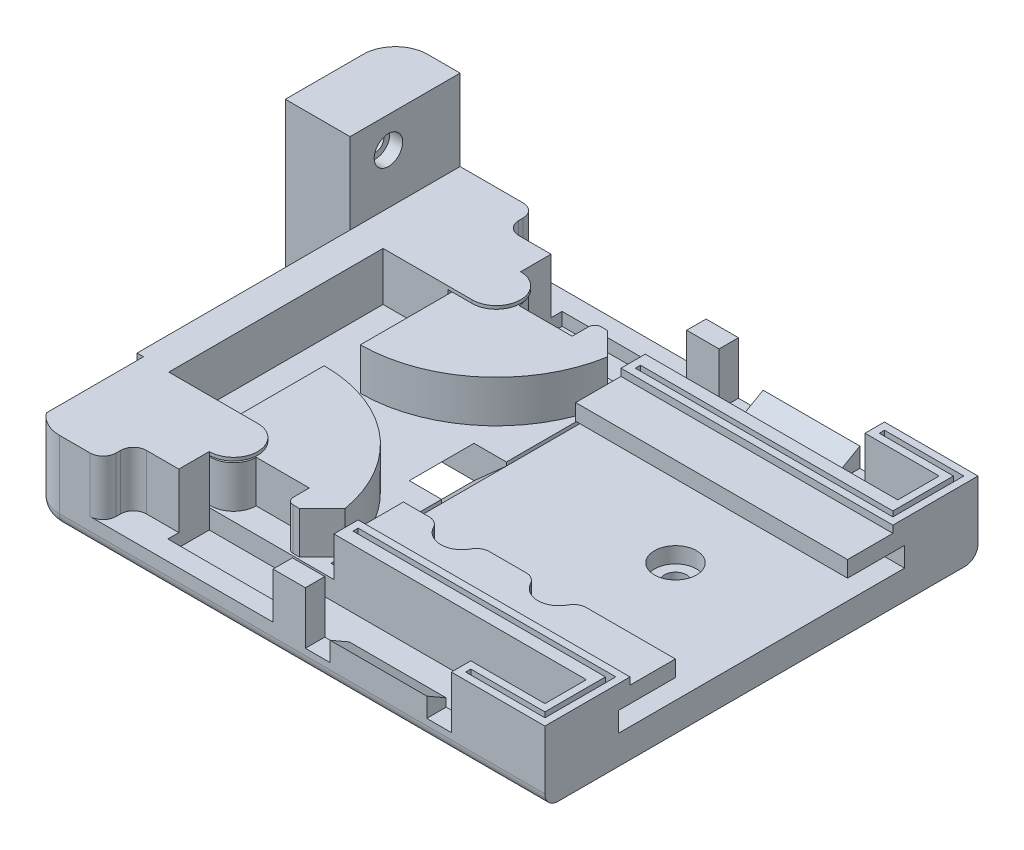
SolidWorks part; units mm, degrees
ref_plane "Front Plane" through (0, 0, 0) normal (0, 0, 1) x (1, 0, 0)
ref_plane "Top Plane" through (0, 0, 0) normal (0, 1, 0) x (1, 0, 0)
ref_plane "Right Plane" through (0, 0, 0) normal (1, 0, 0) x (0, 0, -1)
sketch "Sketch1" plane through (0, 0, 0) normal (0, 1, 0) x (1, 0, 0)
  line L0 (5, 33.45) -> (5, 16.9)
  line L1 (0, 0) -> (80, 0)
  line L2 (0, 0) -> (0, 33.45)
  line L3 (0, 33.45) -> (80, 33.45)
  line L4 (80, 0) -> (80, 33.45)
  line L5 (5, 16.9) -> (15, 16.9)
  line L6 (15, 16.9) -> (15, 13.15)
  line L7 (18.75, 9.4) -> (18.75, 3)
  line L8 (18.75, 3) -> (77, 3)
  line L10 (18.75, 9.4) -> (77, 9.4)
  line L11 (77, 3) -> (77, 9.4)
  line L12 (38, 9.4) -> (80, 9.4)
  line L13 (38, 9.4) -> (38, 13.15)
  line L14 (38, 13.15) -> (80, 13.15)
  line L15 (80, 9.4) -> (80, 13.15)
  circle A0 centre (18.75, 13.15) radius 2.25
  arc A1 (15, 13.15) -> (18.75, 9.4) centre (18.75, 13.15) ccw
  circle A2 centre (18.75, 13.15) radius 3.75 construction
  point P12 (10, 16.9)
  dimension "D11" = 1.5
  dimension "D12" = 4.5
  dimension "D1" = 33.45
  dimension "D2" = 80
  dimension "D3" = 3
  dimension "D4" = 3
  dimension "D5" = 7.5
  dimension "D6" = 6.4
  dimension "D7" = 5
  dimension "D8" = 10
  dimension "D9" = 3.75
  dimension "D10" = 42
extrude "Boss-Extrude1" add sketch "Sketch1" along normal blind 7.5 contours A1 L6 L5 L0 L3 L2 L1 L4 L12 L11 L8 L7 | A0 | L14 L13 L10 L12 L4 region at (4.1329, 0, -25.175) region at (59, 0, -11.275) region at (18.75, 0, -13.15)
sketch "Sketch2" plane through (0, 0, 0) normal (0, -1, 0) x (-1, 0, 0)
  line L1 (0, 0) -> (-80, 0)
  line L2 (0, 0) -> (0, 33.45)
  line L3 (0, 33.45) -> (-80, 33.45)
  line L4 (-80, 0) -> (-80, 33.45)
extrude "Boss-Extrude2" add sketch "Sketch2" along normal blind 5
sketch "Sketch3" plane through (0, 0, 0) normal (0, 0, 1) x (1, 0, 0)
  line L0 (0, 7.5) -> (80, 7.5) construction
  line L1 (63, 6.1) -> (43, 6.1)
  line L3 (63, 1.5) -> (43, 1.5)
  line L4 (43, 6.1) -> (43, 1.5)
  line L5 (38, 7.5) -> (38, 0)
  line L6 (80, -5) -> (80, 7.5) construction
  line L7 (63, 6.1) -> (63, 1.5)
  line L8 (43, 1.5) -> (46.8, 1.5)
  line L9 (43, 1.5) -> (43, -2)
  line L10 (43, -2) -> (46.8, -2)
  line L11 (46.8, 1.5) -> (46.8, -2)
  line L12 (38, 0) -> (18.75, 0)
  line L13 (38, 0) -> (38, 7.5)
  line L14 (38, 7.5) -> (18.75, 7.5)
  line L15 (18.75, 0) -> (18.75, 7.5)
  line L20 (63, 1.5) -> (65.55, 1.5)
  line L21 (46.8, -2) -> (47.1, 1.5)
  line L22 (47.1, 1.5) -> (46.8, 1.5)
  line L23 (65.55, 1.5) -> (65.55, 6.1)
  line L24 (65.55, 6.1) -> (63, 6.1)
  line L25 (80, -5) -> (0, -5) construction
  line L26 (65.55, 1.5) -> (61.75, 1.5)
  line L27 (65.55, 1.5) -> (65.55, -2)
  line L28 (65.55, -2) -> (61.75, -2)
  line L29 (61.75, 1.5) -> (61.75, -2)
  line M15 (80, 7.5) -> (0, 7.5)
  dimension "D1" = 4.6
  dimension "D2" = 3
  dimension "D3" = 20
  dimension "D4" = 7.5
  dimension "D5" = 5
  dimension "D6" = 42
  dimension "D7" = 3.8
  dimension "D8" = 19.25
  dimension "D9" = 3.5
  dimension "D10" = 14.45
  dimension "D11" = 3.8
  dimension "D12" = 3.5
  dimension "D13" = 0.3
extrude "Cut-Extrude1" cut sketch "Sketch3" against normal blind 3 contours L15 L12 L5 M15 | L1 L4 L3 | L23 L24 L7 L20 | L20 L29 L28 L27 | L9 L8 L11 L10 region at (53, 3.8, 0) region at (64.275, 3.8, 0) region at (63.65, -0.25, 0) region at (28.375, 3.75, 0)
sketch "Sketch4" plane through (0, 0, 0) normal (0, 1, 0) x (1, 0, 0)
  line L1 (18.75, 9.4) -> (77, 9.4)
  line L2 (18.75, 9.4) -> (18.75, 3)
  line L3 (18.75, 3) -> (77, 3)
  line L4 (77, 9.4) -> (77, 3)
extrude "Cut-Extrude2" cut sketch "Sketch4" against normal blind 3
sketch "Sketch5" plane through (80, 0, 0) normal (1, 0, 0) x (0, 0, -1)
  line L0 (13.15, 7.5) -> (13.15, 0) construction
  line L1 (13.15, 5) -> (20.15, 5)
  line L2 (13.15, 5) -> (13.15, 2.5)
  line L3 (13.15, 2.5) -> (20.15, 2.5)
  line L4 (20.15, 5) -> (20.15, 2.5)
  line L5 (0, 7.5) -> (13.15, 7.5) construction
  dimension "D1" = 2.5
  dimension "D2" = 2.5
  dimension "D3" = 7
extrude "Boss-Extrude3" add sketch "Sketch5" against normal up to surface (42 mm away) up to face at (38, 3.75, -11.275)
sketch "Sketch6" plane through (0, 0, 0) normal (0, 1, 0) x (1, 0, 0)
  line L0 (38, 13.15) -> (80, 13.15) construction
  line L1 (80, 33.45) -> (35.6, 33.45)
  line L2 (80, 33.45) -> (80, 13.15)
  line L3 (80, 13.15) -> (35.6, 13.15)
  line L4 (35.6, 33.45) -> (35.6, 13.15)
  dimension "D1" = 44.4
extrude "Cut-Extrude3" cut sketch "Sketch6" against normal blind 0.55
sketch "Sketch7" plane through (0, 0, 0) normal (0, 1, 0) x (1, 0, 0)
  line L0 (15.25, 13.15) -> (15.25, 9.65)
  line L1 (15.25, 9.65) -> (18.75, 9.65)
  line L2 (15.25, 9.65) -> (36.25, 9.65)
  line L3 (15.25, 9.65) -> (15.25, 30.65)
  line L4 (22.25, 13.15) -> (35.9563, 13.15)
  line L5 (35.9563, 13.15) -> (32.4563, 9.65)
  line L6 (30.4563, 9.65) -> (26.9563, 13.15)
  line L7 (30.4563, 9.65) -> (30.4563, 13.15)
  circle A0 centre (18.75, 13.15) radius 2.6
  circle A1 centre (18.75, 13.15) radius 3.5
  circle A2 centre (15.25, 9.65) radius 21
  line M8 (38, 13.15) -> (35.6, 13.15)
  line M9 (35.6, 13.15) -> (35.6, 33.45)
  dimension "D1" = 5.2
  dimension "D2" = 7
  dimension "D4" = 42
  dimension "D3" = 3.5
  dimension "D5" = 2
  dimension "D6" = 45
extrude "Boss-Extrude4" add sketch "Sketch7" along normal blind 6.5 from offset 0.1 separate body contours L4 A2 L3 A1 | L6 L2 L5 L4 | A1 A0 | A2 M8 M9 region at (24.1149, 0, -20.9339) region at (18.75, 0, -16.551) region at (35.723, 0, -13.7293) region at (32.4674, 0, -11.6722)
sketch "Sketch8" plane through (0, 7.5, 0) normal (0, 1, 0) x (1, 0, 0)
  line L0 (15, 16.9) -> (15, 13.15)
  line L1 (15, 16.9) -> (18.75, 16.9)
  arc A0 (15, 13.15) -> (18.75, 16.9) centre (18.75, 13.15) ccw
extrude "Boss-Extrude5" add sketch "Sketch8" against normal blind 0.5
sketch "Sketch9" plane through (0, 7.5, 0) normal (0, 1, 0) x (1, 0, 0)
  line L0 (18.75, 9.4) -> (18.75, 0) construction
  line L1 (18.75, 4.7) -> (11.75, 4.7)
  line L2 (18.75, 4.7) -> (18.75, 0)
  line L3 (18.75, 0) -> (11.75, 0)
  line L4 (11.75, 4.7) -> (11.75, 0)
  line L5 (0, 0) -> (18.75, 0) construction
  dimension "D1" = 7
extrude "Cut-Extrude4" cut sketch "Sketch9" against normal up to surface (7.5 mm away) up to face at (28.375, 0, -1.5)
sketch "Sketch10" plane through (0, 0, 0) normal (0, 1, 0) x (1, 0, 0)
  line L0 (18.75, 4.7) -> (18.75, 3)
  line L1 (18.75, 3) -> (38, 3)
  line L2 (38, 3) -> (38, 0)
  line L3 (38, 0) -> (11.75, 0)
  line L4 (11.75, 0) -> (11.75, 4.7)
  line L5 (11.75, 4.7) -> (18.75, 4.7)
extrude "Cut-Extrude5" cut sketch "Sketch10" against normal blind 1
fillet "Fillet2" radius 2 2 edges at (11.75, 3.25, 0) (11.75, 3.25, -4.7)
fillet "Fillet3" radius 1 1 edges at (30.4563, 3.35, -9.65)
fillet "-Lower corner fillets (deleted due to new extruding)" [suppressed] radius 5
fillet "Long side fillets (deleted due to new stabilizing tab)" [suppressed] radius 2
sketch "Sketch15" plane through (0, 0, -33.45) normal (0, 0, -1) x (-1, 0, 0)
  line L0 (-35.6, 0) -> (-30.6, 0)
  line L1 (-5, 0) -> (-35.6, 0) construction
  line L2 (-30.6, 0) -> (-25.6, -5)
  line L3 (0, -5) -> (-80, -5) construction
  line L4 (-25.6, -5) -> (-30.6, -5)
  line L5 (-30.6, -5) -> (-35.6, -0.55)
  line L6 (-35.6, -0.55) -> (-35.6, 0)
  line L7 (-25.6, -5) -> (0, -5)
  line L8 (0, -5) -> (0, -2)
  line L9 (0, -5) -> (0, 7.5) construction
  line L10 (0, -2) -> (-28.6, -2)
  line M6 (-80, -5) -> (0, -5)
  line M8 (0, -5) -> (0, 7.5)
  line M11 (-5, 0) -> (-35.6, 0)
  line M12 (-35.6, 0) -> (-35.6, -0.55)
  dimension "D1" = 5
  dimension "D2" = 5
  dimension "D3" = 135
  dimension "D4" = 3
extrude "Cut-Extrude11" cut sketch "Sketch15" against normal blind 5 contours L5 L2 M6 M11 M12 | L10 L2 M8 M6 region at (30.7738, -2.4661, -33.45) region at (13.5638, -3.4723, -33.45)
sketch "Sketch16" plane through (46.8, 0, 0) normal (-1, 0, 0) x (0, 0, 1)
  line L0 (-3, -0.75) -> (0, 0.9821)
  line L1 (-3, 1.5) -> (-3, -2) construction
  line L2 (0, 1.5) -> (0, -2) construction
  line L3 (0, 0.9821) -> (0, 1.5)
  line L4 (0, 1.5) -> (-3, 1.5)
  line L5 (-3, 1.5) -> (-3, -0.75)
  line L6 (-3, -2) -> (0, -2) construction
  line M3 (0, 1.5) -> (-3, 1.5)
  line M4 (-3, 1.5) -> (-3, -2)
  dimension "D1" = 1.25
  dimension "D2" = 30
extrude "Cut-Extrude12" cut sketch "Sketch16" against normal up to next (14.95 mm away) contours L0 M4 M3 region at (46.8, 0.7177, -1.8129)
sketch "Sketch17" plane through (0, 7.5, 0) normal (0, 1, 0) x (1, 0, 0)
  line L1 (80, 0) -> (38, 0)
  line L2 (80, 0) -> (80, 13.15)
  line L3 (80, 13.15) -> (38, 13.15)
  line L4 (38, 0) -> (38, 13.15)
extrude "Cut-Extrude13" cut sketch "Sketch17" against normal up to surface (1.4 mm away) up to face at (54.275, 6.1, -1.5)
sketch "Sketch18" plane through (0, 6.1, 0) normal (0, 1, 0) x (1, 0, 0)
  line L0 (38, 13.15) -> (80, 13.15)
  line L1 (80, 13.15) -> (80, 0)
  line L2 (80, 0) -> (65.55, 0)
  line L3 (65.55, 0) -> (65.55, 3)
  line L4 (65.55, 3) -> (77, 3)
  line L5 (77, 3) -> (77, 10.15)
  line L6 (77, 10.15) -> (38, 10.15)
  line L7 (38, 9.4) -> (38, 13.15) construction
  line L8 (38, 10.15) -> (38, 13.15)
  line L9 (39.1, 11.25) -> (39.1, 12.05)
  line L10 (39.1, 12.05) -> (78.9, 12.05)
  line L11 (78.9, 12.05) -> (78.9, 1.1)
  line L12 (78.9, 1.1) -> (66.65, 1.1)
  line L13 (66.65, 1.1) -> (66.65, 1.9)
  line L14 (66.65, 1.9) -> (78.1, 1.9)
  line L15 (78.1, 1.9) -> (78.1, 11.25)
  line L16 (78.1, 11.25) -> (39.1, 11.25)
  dimension "D1" = 3
  dimension "D2" = 1.1
extrude "Cut-Extrude14" cut sketch "Sketch18" against normal blind 1.7 contours L16 L15 L14 L13 L12 L11 L10 L9 region at (39.5128, 6.1, -11.65)
mirror "Mirror1" about plane through (0, -5, -33.45) normal (0, 0, 1) of bodies 143
ref_plane "Plane14" through (0, 0, -33.45) normal (0, 0, 1) x (1, 0, 0)
mirror "Mirror2" about plane through (0, 0, -33.45) normal (0, 0, 1) of bodies 108
sketch "Sketch19" plane through (0, 0, 0) normal (0, 1, 0) x (1, 0, 0)
  line L0 (5, 33.45) -> (80, 33.45)
  line L1 (5, 50) -> (5, 16.9) construction
  line L2 (80, 13.15) -> (80, 53.75) construction
  line L3 (80, 33.45) -> (5.6792, 33.45) construction
  line L4 (18, 20.575) -> (18, 33.45) construction
  line L7 (61.6, 20.575) -> (61.6, 33.45) construction
  line L8 (0, 0) -> (0, 66.9) construction
  line L9 (-6.875, 33.45) -> (6.875, 33.45) construction
  circle A0 centre (18, 38.575) radius 3.25
  circle A1 centre (18, 20.575) radius 3.25
  circle A2 centre (3, 20.575) radius 3.25
  circle A3 centre (18, 20.575) radius 1.7
  circle A4 centre (18, 38.575) radius 1.7
  circle A5 centre (3, 20.575) radius 1.7
  circle A6 centre (61.6, 38.575) radius 3.25
  circle A7 centre (61.6, 20.575) radius 3.25
  circle A8 centre (46.6, 20.575) radius 3.25
  circle A9 centre (61.6, 20.575) radius 1.7
  circle A10 centre (61.6, 38.575) radius 1.7
  circle A11 centre (46.6, 20.575) radius 1.7
  point P1 (80, 33.45)
  point P32 (0, 0)
  point P33 (0, 0)
  point P34 (0, 0)
  point P35 (0, 0)
  point P36 (0, 0)
  point P37 (0, 0)
  point P38 (0, 0)
  point P41 (28, 33.45)
  point P44 (71.6, 33.45)
  point P45 (28, 24.45)
  point P46 (28, 42.45)
  dimension "D10" = 6.5
  dimension "D11" = 3.4
  dimension "D1" = 15
  dimension "D2" = 15
  dimension "D3" = 18
  dimension "D4" = 15
  dimension "D5" = 15
  dimension "D6" = 18
  dimension "D8" = 3
  dimension "D7" = 28.6
  dimension "D9" = 12.875
extrude "Cut-Extrude15" cut sketch "Sketch19" against normal blind 3 contours A1 A3 | A3 | A6 A10 | A10 | A7 A9 | A9 | A8 A11 | A11 region at (14.8419, 0, -20.575) region at (18, 0, -20.575) region at (58.4419, 0, -38.575) region at (58.4419, 0, -20.575) region at (43.4419, 0, -20.575) region at (61.6, 0, -20.575) region at (61.6, 0, -38.575) region at (46.6, 0, -20.575)
sketch "Sketch20" plane through (0, -0.55, 0) normal (0, 1, 0) x (1, 0, 0)
  circle A0 centre (46.6, 20.575) radius 1.7
  circle A1 centre (18, 20.575) radius 1.7
  circle A5 centre (61.6, 38.575) radius 1.7
  circle A6 centre (61.6, 38.575) radius 3.25 construction
  circle A7 centre (46.6, 20.575) radius 3.25 construction
  circle A8 centre (61.6, 20.575) radius 1.7
  circle A9 centre (61.6, 38.575) radius 3.25 construction
  dimension "D1" = 3.4
extrude "Cut-Extrude16" cut sketch "Sketch20" against normal through all contours A0 | A1 | A5 | A8 region at (46.6, -0.55, -20.575) region at (18, -0.55, -20.575) region at (61.6, -0.55, -38.575) region at (61.6, -0.55, -20.575)
sketch "Sketch26" plane through (0, -5, 0) normal (0, 1, 0) x (1, 0, 0)
  line L0 (-10, 66.9) -> (-10, 49.9)
  line L2 (-10, 49.9) -> (0, 49.9)
  line L3 (0, 0) -> (0, 66.9) construction
  line L16 (0, 0) -> (9.75, 0)
  line L17 (11.75, 2) -> (11.75, 2.7)
  line L18 (13.75, 4.7) -> (18.75, 4.7)
  line L19 (18.75, 4.7) -> (18.75, 9.4)
  line L20 (18.75, 16.9) -> (5, 16.9)
  line L21 (5, 16.9) -> (5, 50)
  line L22 (5, 50) -> (18.75, 50)
  line L23 (18.75, 57.5) -> (18.75, 62.2)
  line L24 (18.75, 62.2) -> (13.75, 62.2)
  line L25 (11.75, 64.2) -> (11.75, 64.9)
  line L26 (9.75, 66.9) -> (0, 66.9)
  line L27 (0, 66.9) -> (0, 0)
  line L38 (-10, 66.9) -> (0, 66.9)
  line L39 (0, 66.9) -> (0, 49.9)
  arc A6 (9.75, 0) -> (11.75, 2) centre (9.75, 2) ccw
  arc A7 (13.75, 4.7) -> (11.75, 2.7) centre (13.75, 2.7) ccw
  arc A8 (18.75, 9.4) -> (18.75, 16.9) centre (18.75, 13.15) ccw
  arc A9 (18.75, 50) -> (18.75, 57.5) centre (18.75, 53.75) ccw
  arc A10 (11.75, 64.2) -> (13.75, 62.2) centre (13.75, 64.2) ccw
  arc A11 (11.75, 64.9) -> (9.75, 66.9) centre (9.75, 64.9) ccw
  dimension "D2" = 17
  dimension "D3" = 10
  dimension "D1" = 0
extrude "Boss-Extrude11" add sketch "Sketch26" along normal blind 25
sketch "Sketch32" plane through (0, 0, 0) normal (-1, 0, 0) x (0, 0, 1)
  line L0 (-49.9, 7.5) -> (-66.9, 7.5)
  line L1 (-66.9, 7.5) -> (-66.9, 20)
  line L2 (-66.9, 20) -> (-49.9, 20)
  line L3 (-49.9, 20) -> (-49.9, 7.5)
  line L4 (-66.9, 20) -> (-49.9, 20) construction
  line L5 (-66.9, 20) -> (-66.9, 7.5) construction
  point P8 (0, 0)
  point P9 (-49.9, 22.5)
  point P10 (0, 0)
  point P13 (0, 0)
  point P14 (0, 0)
  point P15 (-67.9801, 7.5)
extrude "Boss-Extrude12" add sketch "Sketch32" along normal blind 3.4
sketch "Sketch33" plane through (-10, 0, 0) normal (-1, 0, 0) x (0, 0, 1)
  point P1 (-55.825, 15.2375)
hole_wizard "CBORE for M2 SHCS1" positions "Sketch38" profile "Sketch39" counterbore size "M2" standard "ANSI Metric" end condition through all
sketch "Sketch38" plane through (0, 0, 0) normal (1, 0, 0) x (0, 0, -1)
  point P3 (55.825, 15.2375)
  point P7 (0, 0)
sketch "Sketch39" plane through (0, 15.2375, -55.825) normal (0, 1, 0) x (0, 0, -1)
  line L0 (0, 0) -> (0, 10)
  line L1 (0, 10) -> (1.3, 10)
  line L3 (1.3, 10) -> (1.3, 2)
  line L4 (1.3, 2) -> (2.2, 2)
  line L5 (2.2, 2) -> (2.2, 0)
  line L7 (2.2, 0) -> (0, 0)
  line L11 (0, -6.35) -> (0, 107.95) construction
  dimension "Thru Hole Dia." = 2.6
  dimension "Thru Hole Depth" = 10
  dimension "C'Bore Dia." = 4.4
  dimension "C'Bore Depth" = 2
sketch "Sketch37" [suppressed] plane through (0, 7.5, 0) normal (0, -1, 0) x (1, 0, 0)
  line L0 (-3.4, -49.9) -> (0, -49.9)
  line L1 (0, -49.9) -> (0, -66.9)
  line L2 (0, -66.9) -> (-3.4, -66.9)
  line L3 (-3.4, -66.9) -> (-3.4, -49.9)
fillet "Fillet13" radius 5 1 edges at (0, 1.25, 0)
fillet "Fillet14" radius 5 1 edges at (-10, 7.5, -66.9)
fillet "Long side fillet (1)" radius 2 3 edges at (42.5, -5, 0) (0, -5, -16.725) (1.4645, -5, -1.4645)
fillet "Long side fillet (2)" radius 2 3 edges at (37.5, -5, -66.9) (-10, -5, -55.9) (-8.5355, -5, -65.4355)
sketch "Sketch40" plane through (0, -5, 0) normal (0, -1, 0) x (1, 0, 0)
  line L0 (18, -20.575) -> (18, -38.45) construction
  line L1 (-68.777, -29.5125) -> (112.777, -29.5125) construction
  line L4 (-5, -66.9) -> (0, -66.9)
  line L5 (0, -66.9) -> (0, -49.9)
  line L6 (0, -49.9) -> (-10, -49.9)
  line L7 (-10, -49.9) -> (-10, -61.9)
  line L8 (-5, -66.9) -> (0, -66.9) construction
  line L10 (0, -49.9) -> (-10, -49.9) construction
  line L11 (-10, -49.9) -> (-10, -61.9) construction
  line L18 (30.6, -38.45) -> (0, -38.45) construction
  line L20 (0, 0) -> (1, 0)
  line L21 (0, 0) -> (0, -17)
  line L22 (0, -17) -> (1, -17)
  line L23 (0, -66.9) -> (0, -49.9)
  line L24 (1, 0) -> (1, -17)
  arc A4 (-10, -61.9) -> (-5, -66.9) centre (-5, -61.9) ccw
  arc A5 (-10, -61.9) -> (-5, -66.9) centre (-5, -61.9) ccw
  point P7 (18, -29.5125)
  point P14 (18, -29.5125)
  line M41 (0, -38.45) -> (0, -49.9)
  dimension "D2" = 1
  dimension "D1" = 0
extrude "Cut-Extrude17" cut sketch "Sketch40" against normal up to surface (12.5 mm away) contours L24 L22 M41 region at (0.5, -5, -8.5) up to face at (11.3982, 7.5, -32.7982)
sketch "Sketch41" plane through (80, 0, 0) normal (1, 0, 0) x (0, 0, -1)
  line L0 (13.15, -0.55) -> (53.75, -0.55) construction
  line L1 (55.55, 2.5) -> (11.35, 2.5)
  line L2 (55.55, 2.5) -> (55.55, -0.55)
  line L3 (55.55, -0.55) -> (11.35, -0.55)
  line L4 (11.35, 2.5) -> (11.35, -0.55)
  line L5 (13.15, 2.5) -> (20.15, 2.5) construction
  point P6 (33.45, -0.55)
  dimension "D1" = 44.2
extrude "Cut-Extrude18" cut sketch "Sketch41" against normal up to surface (44.4 mm away) up to face at (35.6, -0.275, -20.8)
extrude "Cut-Extrude19" cut sketch "Sketch19<4>" along normal up to surface (5 mm away) contours A7 A9 | A9 | A8 A11 | A11 region at (58.4419, 0, -20.575) region at (43.4419, 0, -20.575) region at (61.6, 0, -20.575) region at (46.6, 0, -20.575) up to face at (59, 5, -16.65)
sketch "Sketch19<4>" plane through (0, 0, 0) normal (0, 1, 0) x (1, 0, 0) same geometry as "Sketch19"
fillet "Fillet15" radius 2 4 edges at (64.8221, 3.75, -20.15) (58.3779, 3.75, -20.15) (49.8221, 3.75, -20.15) (43.3779, 3.75, -20.15)
equation "\"D9@Sketch19\"=\"D6@Sketch19\"/2+3.875"
